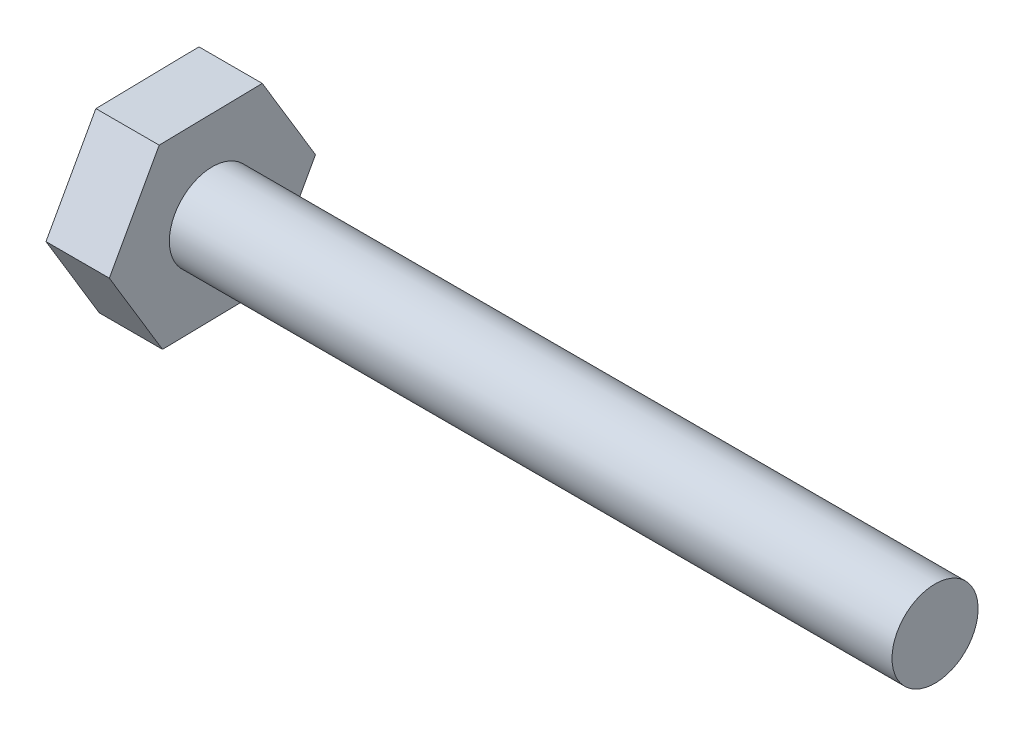
SolidWorks part; units mm, degrees
ref_plane "Front Plane" through (0, 0, 0) normal (0, 0, 1) x (1, 0, 0)
ref_plane "Top Plane" through (0, 0, 0) normal (0, 1, 0) x (1, 0, 0)
ref_plane "Right Plane" through (0, 0, 0) normal (1, 0, 0) x (0, 0, -1)
sketch "Sketch1" plane through (0, 0, 0) normal (1, 0, 0) x (0, 0, -1)
  line L1 (4.1302, -6.8538) -> (8.0007, 0.15)
  line L2 (8.0007, 0.15) -> (3.8704, 7.0038)
  line L3 (3.8704, 7.0038) -> (-4.1302, 6.8538)
  line L4 (-4.1302, 6.8538) -> (-8.0007, -0.15)
  line L5 (-8.0007, -0.15) -> (-3.8704, -7.0038)
  line L6 (-3.8704, -7.0038) -> (4.1302, -6.8538)
  circle A0 centre (0, 0) radius 6.93 construction
  circle A1 centre (0, 0) radius 3.34
  dimension "D2" = 6.68
  dimension "D1" = 6.93
extrude "Boss-Extrude1" add sketch "Sketch1" along normal blind 4.9138 contours A1 | L5 L6 L1 L2 L3 L4 A1 | A1 | L1 L2 L3 L4 L5 L6 region at (0, -6.7162, -0.1259) region at (0, 0, 0)
extrude "Boss-Extrude2" add sketch "Sketch1<3>" along normal blind 61 contours A1 region at (0, 0, 0)
sketch "Sketch1<3>" plane through (0, 0, 0) normal (1, 0, 0) x (0, 0, -1) same geometry as "Sketch1"
